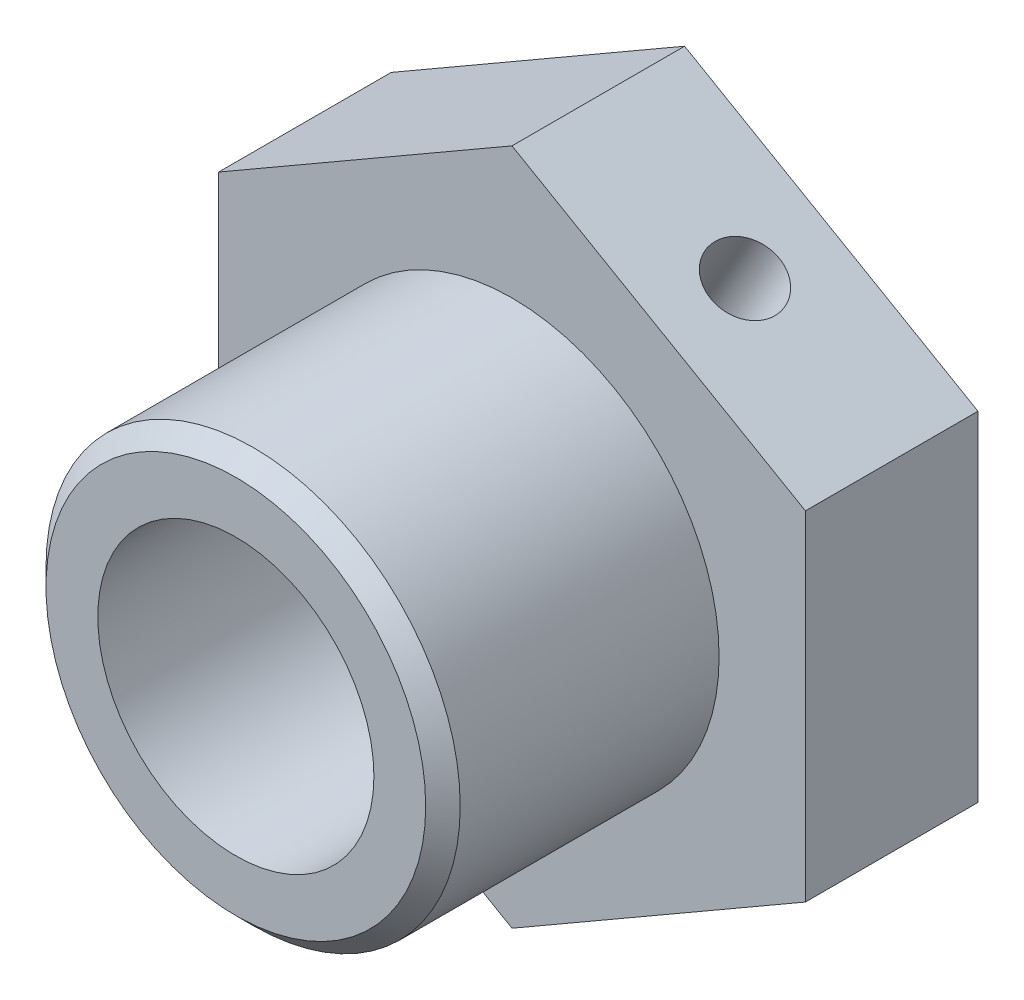
SolidWorks part; units mm, degrees
ref_plane "Alzado" through (0, 0, 0) normal (0, 0, 1) x (1, 0, 0)
ref_plane "Planta" through (0, 0, 0) normal (0, 1, 0) x (1, 0, 0)
ref_plane "Vista lateral" through (0, 0, 0) normal (1, 0, 0) x (0, 0, -1)
sketch "Croquis1" plane through (0, 0, 0) normal (0, 0, 1) x (1, 0, 0)
  line L1 (0, 9.815) -> (-8.5, 4.9075)
  line L2 (-8.5, 4.9075) -> (-8.5, -4.9075)
  line L3 (-8.5, -4.9075) -> (0, -9.815)
  line L4 (0, -9.815) -> (8.5, -4.9075)
  line L5 (8.5, -4.9075) -> (8.5, 4.9075)
  line L6 (8.5, 4.9075) -> (0, 9.815)
  circle A0 centre (0, 0) radius 8.5 construction
  dimension "D1" = 17
extrude "Saliente-Extruir1" add sketch "Croquis1" along normal blind 5
sketch "Croquis2" plane through (0, 0, 5) normal (0, 0, 1) x (1, 0, 0)
  circle A0 centre (0, 0) radius 6
  dimension "D1" = 12
extrude "Saliente-Extruir2" add sketch "Croquis2" along normal blind 8
sketch "Croquis3" plane through (0, 0, 13) normal (0, 0, 1) x (1, 0, 0)
  circle A0 centre (0, 0) radius 4
  dimension "D1" = 8
extrude "Cortar-Extruir1" cut sketch "Croquis3" against normal through all
chamfer "Chaflán1" distance 0.5 angle 45 1 edges at (6, 0, 13)
sketch "Croquis4" plane through (4.25, 7.3612, 0) normal (0.5, 0.866, 0) x (0.866, -0.5, 0)
  line L0 (4.9075, 0) -> (-4.9075, 0) construction
  circle A0 centre (0, -2.5) radius 1
  dimension "D1" = 2
  dimension "D2" = 2.5
extrude "Cortar-Extruir2" cut sketch "Croquis4" against normal through all
